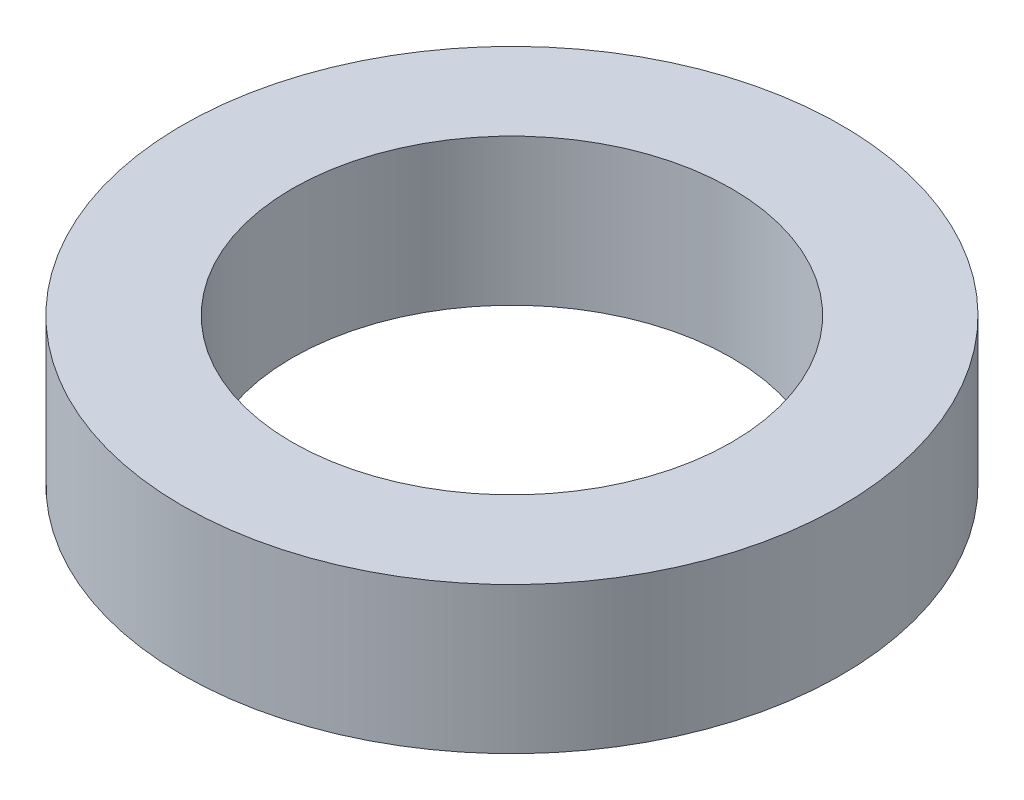
SolidWorks part; units mm, degrees
ref_plane "Front Plane" through (0, 0, 0) normal (0, 0, 1) x (1, 0, 0)
ref_plane "Top Plane" through (0, 0, 0) normal (0, 1, 0) x (1, 0, 0)
ref_plane "Right Plane" through (0, 0, 0) normal (1, 0, 0) x (0, 0, -1)
sketch "Sketch1" plane through (0, 0, 0) normal (0, 1, 0) x (1, 0, 0)
  circle A0 centre (0, 0) radius 22.5
  dimension "FLANGE_OD" = 45
extrude "Boss-Extrude1" add sketch "Sketch1" along normal blind 10
sketch "Sketch2" plane through (0, 0, 0) normal (0, 1, 0) x (1, 0, 0)
  circle A0 centre (0, 0) radius 15
  dimension "BORE_D" = 30
extrude "Cut-Extrude1" cut sketch "Sketch2" along normal through all
sketch "Sketch3" plane through (0, 10, 0) normal (0, 1, 0) x (1, 0, 0)
  circle A0 centre (0, 0) radius 9.2042 construction
  circle A1 centre (-9.2042, 0) radius 1.5
  dimension "BOLT_D" = 3
  dimension "BOLT_PCD" = 18.4084
extrude "Cut-Extrude2" cut sketch "Sketch3" against normal blind 6.4034 rebuild error yes
pattern_circular "CirPattern1" count 8 over 360 rebuild error yes
